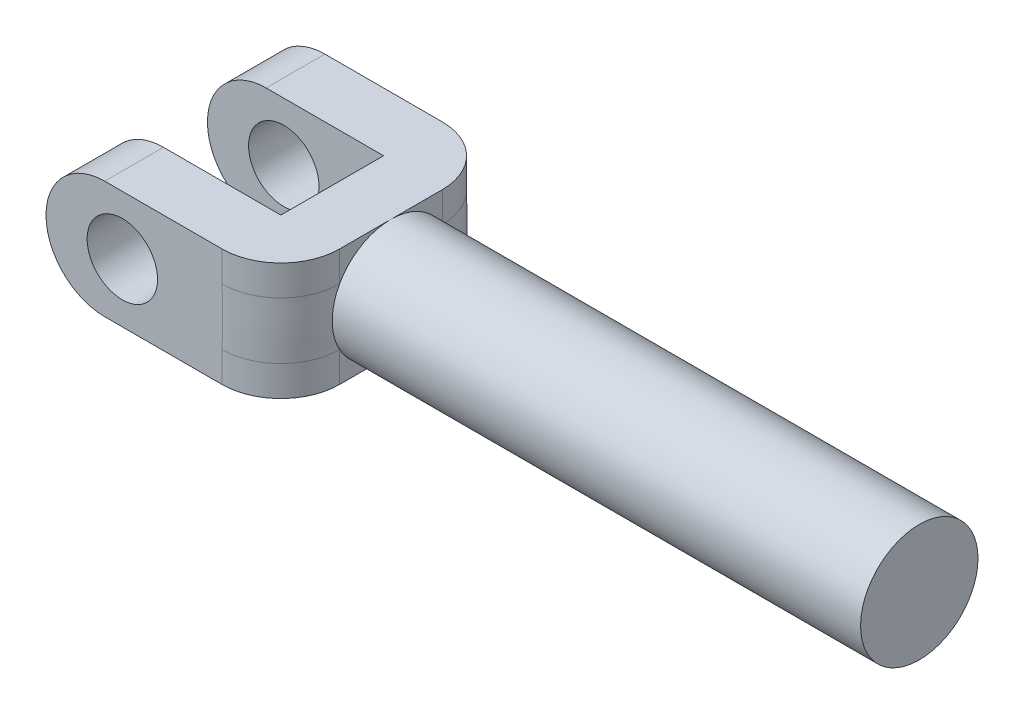
SolidWorks part; units mm, degrees
ref_plane "Front Plane" through (0, 0, 0) normal (0, 0, 1) x (1, 0, 0)
ref_plane "Top Plane" through (0, 0, 0) normal (0, 1, 0) x (1, 0, 0)
ref_plane "Right Plane" through (0, 0, 0) normal (1, 0, 0) x (0, 0, -1)
sketch "Sketch1" plane through (0, 0, 0) normal (1, 0, 0) x (0, 0, -1)
  circle A0 centre (0, 0) radius 1
  dimension "D1" = 2
extrude "Boss-Extrude1" add sketch "Sketch1" along normal blind 10
sketch "Sketch2" plane through (0, 0, 0) normal (0, 1, 0) x (1, 0, 0)
  line L0 (1, 1.875) -> (1, -1.875)
  line L2 (0, 0.875) -> (0, -0.875)
  line L5 (1, -1.875) -> (-3, -1.875)
  line L6 (-3, 1.875) -> (-3, 0.875)
  line L7 (1, 1.875) -> (-3, 1.875)
  line L8 (0, 0.875) -> (-3, 0.875)
  line L10 (-3, -0.875) -> (0, -0.875)
  line L11 (-3, -0.875) -> (-3, -1.875)
  point P1 (0, 0)
  dimension "D1" = 4
  dimension "D2" = 0
extrude "Boss-Extrude2" add sketch "Sketch2" along normal blind 1 and the other way blind 1
fillet "Fillet1" radius 1 6 edges at (-3, 1, -1.375) (-3, -1, -1.375) (-3, -1, 1.375) (-3, 1, 1.375) (1, 0, -1.875) (1, 0, 1.875)
sketch "Sketch3" plane through (0, 0, -1.875) normal (0, 0, -1) x (-1, 0, 0)
  line L0 (0, -1) -> (2, -1) construction
  line L2 (0, 1) -> (0, 0.4841) construction
  circle A0 centre (1.7, 0) radius 0.6
  dimension "D1" = 1.2
  dimension "D2" = 1
  dimension "D3" = 1.7
extrude "Cut-Extrude1" cut sketch "Sketch3" against normal blind 5
